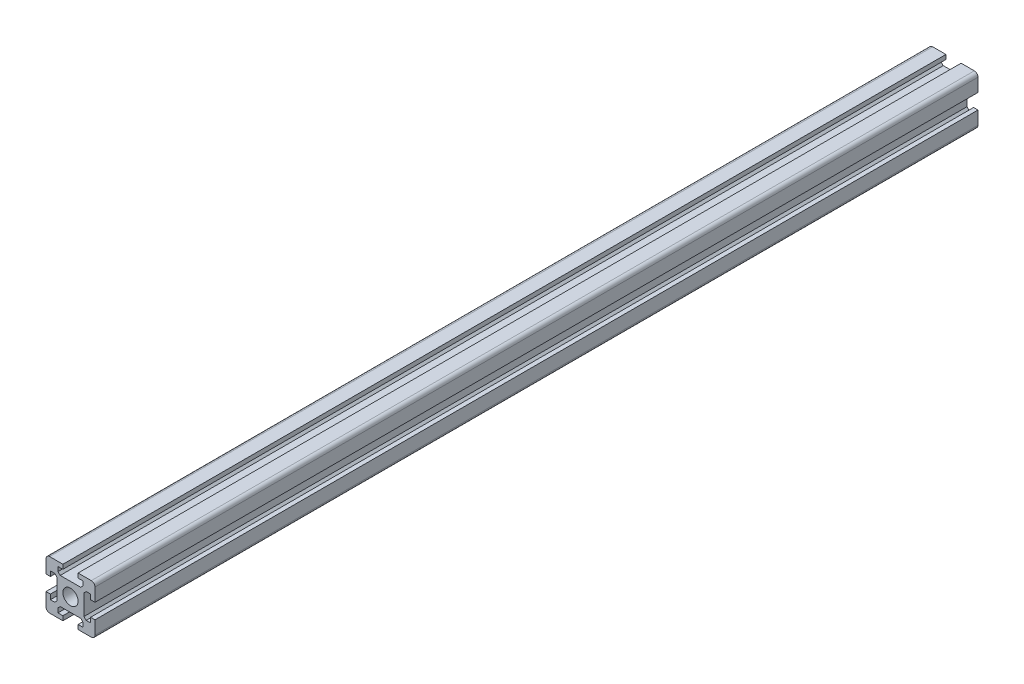
SolidWorks part; units mm, degrees
material "6061 Alloy"
ref_plane "Front Plane" through (0, 0, 0) normal (0, 0, 1) x (1, 0, 0)
ref_plane "Top Plane" through (0, 0, 0) normal (0, 1, 0) x (1, 0, 0)
ref_plane "Right Plane" through (0, 0, 0) normal (1, 0, 0) x (0, 0, -1)
sketch "Sketch1" plane through (0, 0, 0) normal (0, 0, 1) x (1, 0, 0)
  line L0 (-10, 3.1) -> (-8.2, 3.1)
  line L1 (-8.5, 10) -> (-3.1, 10) construction
  line L2 (-10, 8.5) -> (-10, 3.1) construction
  line L3 (-10, -3.1) -> (-10, -8.5) construction
  line L4 (-8.5, -10) -> (-3.1, -10) construction
  line L5 (-10, -3.1) -> (-10, -8.5)
  line L6 (-8.5, -10) -> (-3.1, -10)
  line L7 (-8.2, 3.1) -> (-8.2, 5.1)
  line L8 (-8.2, 5.1) -> (-6.4, 5.1)
  line L9 (-10, -3.1) -> (-8.2, -3.1)
  line L10 (-8.2, -3.1) -> (-8.2, -5.1)
  line L11 (-8.2, -5.1) -> (-6.4, -5.1)
  line L13 (-6.4, 5.1) -> (-5.4929, 4.1929)
  line L14 (-5.4929, 4.1929) -> (-5.4929, -4.1929)
  line L15 (-6.4, -5.1) -> (-5.4929, -4.1929)
  line L16 (-3.1, 10) -> (-3.1, 8.2)
  line L17 (-3.1, 8.2) -> (-5.1, 8.2)
  line L19 (-5.1, 8.2) -> (-5.1, 6.4)
  line L20 (-5.1, 6.4) -> (-4.1929, 5.4929)
  line L21 (-4.1929, 5.4929) -> (4.1929, 5.4929)
  line L22 (4.1929, 5.4929) -> (5.1, 6.4)
  line L23 (5.1, 6.4) -> (5.1, 8.2)
  line L24 (5.1, 8.2) -> (3.1, 8.2)
  line L25 (3.1, 8.2) -> (3.1, 10)
  line L26 (-3.1, -10) -> (-3.1, -8.2)
  line L27 (-3.1, -8.2) -> (-5.1, -8.2)
  line L28 (-5.1, -8.2) -> (-5.1, -6.4)
  line L29 (-5.1, -6.4) -> (-4.1929, -5.4929)
  line L30 (-4.1929, -5.4929) -> (4.1929, -5.4929)
  line L31 (4.1929, -5.4929) -> (5.1, -6.4)
  line L32 (5.1, -6.4) -> (5.1, -8.2)
  line L33 (5.1, -8.2) -> (3.1, -8.2)
  line L34 (3.1, -8.2) -> (3.1, -10)
  line L35 (3.1, -10) -> (8.5, -10)
  line L36 (10, -8.5) -> (10, -3.1)
  line L37 (10, -3.1) -> (8.2, -3.1)
  line L38 (8.2, -3.1) -> (8.2, -5.1)
  line L39 (8.2, -5.1) -> (6.4, -5.1)
  line L40 (6.4, -5.1) -> (5.4929, -4.1929)
  line L41 (5.4929, -4.1929) -> (5.4929, 4.1929)
  line L42 (5.4929, 4.1929) -> (6.4, 5.1)
  line L43 (6.4, 5.1) -> (8.2, 5.1)
  line L44 (8.2, 5.1) -> (8.2, 3.1)
  line L45 (8.2, 3.1) -> (10, 3.1)
  line L46 (10, 3.1) -> (10, 8.5)
  line L47 (8.5, 10) -> (3.1, 10)
  line L48 (-3.1, 10) -> (-8.5, 10)
  line L49 (-10, 8.5) -> (-10, 3.1)
  arc A0 (-8.5, 10) -> (-10, 8.5) centre (-8.5, 8.5) ccw
  arc A1 (-10, -8.5) -> (-8.5, -10) centre (-8.5, -8.5) ccw construction
  arc A2 (8.5, -10) -> (10, -8.5) centre (8.5, -8.5) ccw
  arc A3 (8.5, 10) -> (10, 8.5) centre (8.5, 8.5) cw
  arc A4 (-8.5, -10) -> (-10, -8.5) centre (-8.5, -8.5) cw
  circle A6 centre (0, 0) radius 3.1
  point P0 (0, 0)
  point P44 (-5.2, -3.4858)
  point P47 (-5.2, 3.4858)
  dimension "D3" = 5.4929
  dimension "D5" = 1.5
  dimension "D1" = 6.2
  dimension "D2" = 5.4929
  dimension "D4" = 1.5
  dimension "D6" = 1.5
extrude "Boss-Extrude1" add sketch "Sketch1" along normal blind 360.5
